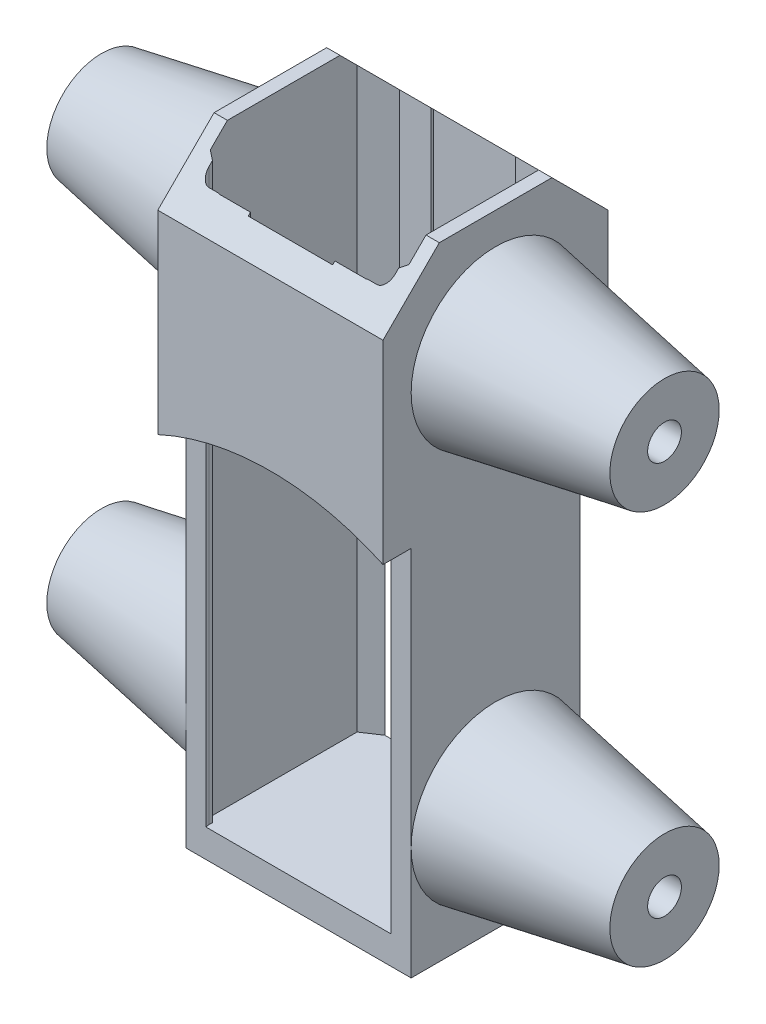
SolidWorks part; units mm, degrees
ref_plane "Front Plane" through (0, 0, 0) normal (0, 0, 1) x (1, 0, 0)
ref_plane "Top Plane" through (0, 0, 0) normal (0, 1, 0) x (1, 0, 0)
ref_plane "Right Plane" through (0, 0, 0) normal (1, 0, 0) x (0, 0, -1)
sketch "Sketch1" plane through (0, 0, 0) normal (0, 1, 0) x (1, 0, 0)
  line L0 (4.7625, -10.1854) -> (8.3298, -10.1854)
  line L5 (-4.7625, 10.1854) -> (-4.7625, 10.4394)
  line L6 (-12.7, -12.7) -> (12.7, -12.7)
  line L7 (4.7625, 10.1854) -> (8.3298, 10.1854)
  line L8 (-8.3298, 10.1854) -> (-11.2014, 8.271)
  line L9 (-8, 10.1) -> (-11, 8.1) construction
  line L10 (0, 0) -> (-11.2014, 0) construction
  line L11 (0, 0) -> (0, 10.4394) construction
  line L12 (-8.3298, -10.1854) -> (-8.3769, -10.154)
  line L13 (8.3298, -10.1854) -> (8.3769, -10.154)
  line L14 (8.3298, 10.1854) -> (11.2014, 8.271)
  line L15 (-8.3298, 10.1854) -> (-4.7625, 10.1854)
  line L16 (-12.7, 12.7) -> (-12.7, -12.7)
  line L17 (12.7, 12.7) -> (12.7, -12.7)
  line L34 (-10.504, -8.7359) -> (-11.2014, -8.271)
  line L35 (8.3769, -10.154) -> (9.4165, -10.154)
  line L36 (9.5863, -10.1409) -> (9.6154, -10.1409)
  line L37 (-9.5863, -10.1409) -> (-9.6154, -10.1409)
  line L38 (-8.75, -10.154) -> (-9.4165, -10.154)
  line L39 (-10.504, -9.1) -> (-10.504, -8.9)
  line L40 (-9.5863, -10.1409) -> (-9.6154, -10.1409)
  line L41 (-8.3769, -10.154) -> (-9.4165, -10.154)
  line L42 (-10.504, -9.1) -> (-10.504, -8.7359)
  line L43 (10.504, -9.1) -> (10.504, -8.7359)
  line L44 (10.504, -8.7359) -> (11.2014, -8.271)
  line L284 (-12.7, 12.7) -> (12.7, 12.7)
  line L286 (-12.7, -12.7) -> (12.7, 12.7) construction
  line L287 (-12.7, 12.7) -> (12.7, -12.7) construction
  line L288 (-8.3298, -10.1854) -> (-4.7625, -10.1854)
  line L289 (-11.2014, -8.271) -> (-11.2014, 8.271)
  line L291 (11.2014, -8.271) -> (11.2014, 8.271)
  line L326 (-4.7625, 10.4394) -> (4.7625, 10.4394)
  line L327 (4.7625, 10.4394) -> (4.7625, 10.1854)
  line L328 (-4.7625, -10.1854) -> (-4.7625, -10.4394)
  line L335 (-4.7625, -10.4394) -> (4.7625, -10.4394)
  line L338 (4.7625, -10.4394) -> (4.7625, -10.1854)
  arc A7 (9.5863, -10.1409) -> (9.4165, -10.154) centre (9.4168, -9.0458) cw
  arc A8 (-9.5863, -10.1409) -> (-9.4165, -10.154) centre (-9.4168, -9.0458) ccw
  arc A9 (-10.504, -9.1) -> (-9.6154, -10.1409) centre (-9.45, -9.1) ccw
  arc A10 (-9.5863, -10.1409) -> (-9.4165, -10.154) centre (-9.4168, -9.0458) ccw
  arc A11 (-10.504, -9.1) -> (-9.6154, -10.1409) centre (-9.45, -9.1) ccw
  arc A12 (10.504, -9.1) -> (9.6154, -10.1409) centre (9.45, -9.1) cw
  point P0 (0, 0)
  point P6 (0, 0)
  point P15 (0, 10.4394)
  point P23 (0, -10.4394)
  dimension "D1" = 25.4
  dimension "D2" = 25.4
  dimension "D3" = 0.254
  dimension "D5" = 9.525
  dimension "D6" = 22.4028
  dimension "D7" = 0.254
  dimension "D8" = 20.3708
  dimension "D9" = 0.254
  dimension "D15" = 0.254
extrude "Boss-Extrude1" add sketch "Sketch1" along normal blind 67.056
sketch "Sketch4" plane through (0, 0, 0) normal (0, -1, 0) x (-1, 0, 0)
  line L1 (12.7, -12.7) -> (-12.7, -12.7)
  line L2 (12.7, -12.7) -> (12.7, 12.7)
  line L3 (12.7, 12.7) -> (-12.7, 12.7)
  line L4 (-12.7, -12.7) -> (-12.7, 12.7)
extrude "Boss-Extrude4" add sketch "Sketch4" along normal blind 3.175
sketch "Sketch5" plane through (0, 0, -12.7) normal (0, 0, -1) x (-1, 0, 0)
  circle A0 centre (0, 11.43) radius 30.1625
  dimension "D2" = 60.325
  dimension "D1" = 11.43
extrude "Cut-Extrude1" cut sketch "Sketch5" against normal blind 3.175
mirror "Mirror1" about plane through (0, 0, 0) normal (0, 0, 1) of "Cut-Extrude1"
sketch "Sketch7" plane through (12.7, 0, 0) normal (1, 0, 0) x (0, 0, -1)
  circle A0 centre (0, 9.525) radius 9.525
  dimension "D2" = 19.05
  dimension "D1" = 9.525
extrude "Boss-Extrude6" add sketch "Sketch7" along normal blind 19.05 draft 10
sketch "Sketch8" plane through (31.75, 0, 0) normal (1, 0, 0) x (0, 0, -1)
  circle A0 centre (0, 9.525) radius 1.905
  dimension "D1" = 3.81
extrude "Cut-Extrude2" cut sketch "Sketch8" against normal blind 12.7
pattern_linear "LPattern1" count 2 spacing 44.45 along (0, 1, 0) of "Boss-Extrude6", "Cut-Extrude2"
mirror "Mirror2" about plane through (0, 0, 0) normal (1, 0, 0) of "LPattern1", "Boss-Extrude6", "Cut-Extrude2"
chamfer "Chamfer1" distance 6.35 angle 45 2 edges at (0, 67.056, 12.7) (0, 67.056, -12.7)
